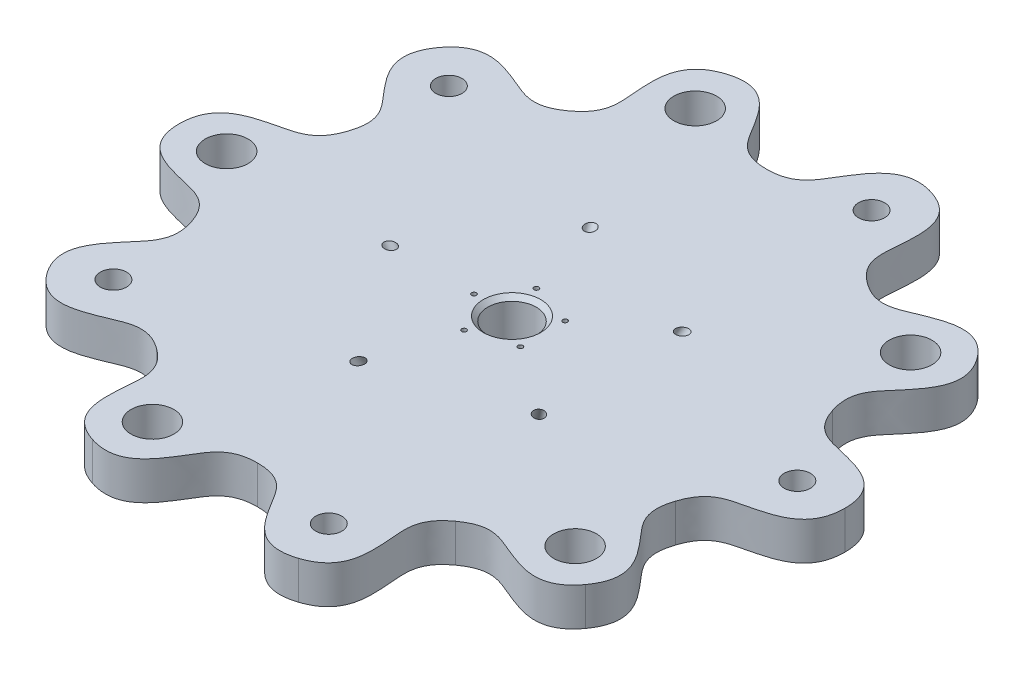
SolidWorks part; units mm, degrees
other "Markup1"
sketch "Sketch22" plane through (67.4, 16.5, 67.4) normal (0.6133, 0.6241, 0.4841) x (0.6587, -0.0661, -0.7495)
sketch "Sketch37" plane through (67.4, 28, 67.4) normal (0.6133, 0.6241, 0.4841) x (0.6587, -0.0661, -0.7495)
other "Markup2"
sketch "Sketch23" plane through (67.4, 26.5, 67.4) normal (0.1362, 0.0894, 0.9866) x (0.9893, -0.0646, -0.1307)
sketch "Sketch38" plane through (67.4, 28, 67.4) normal (0.1362, 0.0894, 0.9866) x (0.9893, -0.0646, -0.1307)
other "Markup5"
sketch "Sketch28" plane through (-67.4, 30.5, 67.4) normal (-0.0176, 0.5562, 0.8308) x (0.9998, 0.0146, 0.0115)
sketch "Sketch39" plane through (-67.4, 28, 67.4) normal (-0.0176, 0.5562, 0.8308) x (0.9998, 0.0146, 0.0115)
material "1023 Carbon Steel Sheet (SS)"
ref_plane "Front Plane" through (0, 0, 0) normal (0, 0, 1) x (1, 0, 0)
ref_plane "Top Plane" through (0, 0, 0) normal (0, 1, 0) x (1, 0, 0)
ref_plane "Right Plane" through (0, 0, 0) normal (1, 0, 0) x (0, 0, -1)
sketch "Sketch1" plane through (0, 0, 0) normal (0, 0, 1) x (1, 0, 0)
  line L5 (-47.4, 0) -> (-47.4, -8)
  line L9 (-7, -8) -> (0, -8)
  line L10 (0, -8) -> (0, 0)
  line L12 (-7, -8) -> (-17.4, -8)
  line L24 (-17.4, -8) -> (-47.4, -8)
  line L25 (-47.4, 0) -> (0, 0)
  dimension "D2" = 8
  dimension "D3" = 47.4
  dimension "D8" = 0
  dimension "D10" = 7
revolve "Revolve1" add sketch "Sketch1" angle 360 about L10
sketch "Sketch4" plane through (0, 0, 0) normal (0, 0, 1) x (1, 0, 0)
  line L0 (0, 0) -> (0, 13.3666) construction
sketch "Sketch2" plane through (0, 0, 0) normal (0, 1, 0) x (1, 0, 0)
  circle A0 centre (-8, 0) radius 0.5
  dimension "D2" = 1
  dimension "D1" = 8
extrude "Fuel holes" cut sketch "Sketch2" against normal up to next from offset 5
pattern_circular "CirPattern1" count 5 over 360 about axis through (0, 0, 0) along (0, 1, 0) of "Fuel holes" reverse direction yes
sketch "Sketch5" plane through (0, 0, 0) normal (1, 0, 0) x (0, 0, -1)
sketch "Sketch19" plane through (0, -8, 0) normal (0, -1, 0) x (1, 0, 0)
  line L0 (-47.4, 0) -> (-70, 0) construction
  line L1 (-56.6312, -41.145) -> (0, 0) construction
  line L4 (0, 0) -> (-66.574, -21.6312) construction
  line L5 (-51.8483, -13.5569) -> (-50.8815, -16.5324) construction
  line L9 (-69, 0) -> (-70, 0)
  line L11 (-53.7996, 39.0877) -> (-54.2257, 38.5013)
  circle A1 centre (0, 0) radius 47.4
  circle A2 centre (0, 0) radius 70 construction
  circle A3 centre (-60, 0) radius 4.5
  circle A4 centre (0, 0) radius 47.4 construction
  circle A5 centre (-48.541, -35.2671) radius 2.75
  circle A6 centre (0, 0) radius 53.5
  circle A8 centre (0, 0) radius 70
  spline S0 degree 3 poles (-50.8815, -16.5324) (-52.4491, -11.7078) (-59.9998, -9.5551) (-70, -7.7496) (-70, 0) knots 0 0 0 0 0.376166 1 1 1 1
  spline S1 degree 3 poles (-50.8815, -16.5324) (-49.3139, -21.357) (-54.1572, -27.5367) (-61.1863, -34.8754) (-56.6312, -41.145) knots 0 0 0 0 0.376166 1 1 1 1
  point P19 (-58.4763, -10.1374)
  point P21 (0, 0)
  point P22 (0, 0)
  circle M22 centre (0, 0) radius 47.4
  dimension "D2" = 9
  dimension "D5" = 5.5
  dimension "D7" = 107
  dimension "D3" = 60
  dimension "D4" = 36
  dimension "D6" = 60
  dimension "D8" = 18
  dimension "D1" = 22.6
extrude "Boss-Extrude2" add sketch "Sketch19" against normal blind 8 contours A6 S1 A8 S0 A3 A5 | S1 S0 A8 | A3 | A5 | A6 M22 region at (-60, -8, 0) region at (-48.541, -8, -35.2671) region at (8.1325, -8, -51.3467) region at (-61.1052, -8, -7.4539) region at (-60.0877, -8, -19.5238)
extrude "Bolt holes" cut sketch "Sketch19<3>" against normal up to surface (8 mm away) contours A3 | A5 up to face at (-1.9721, 0, -7.6085)
sketch "Sketch19<3>" plane through (0, -8, 0) normal (0, -1, 0) x (1, 0, 0) same geometry as "Sketch19"
extrude "Grooves" cut sketch "Sketch19<8>" against normal through all contours S1 S0 A8 region at (-60.0877, -8, -19.5238)
sketch "Sketch19<8>" plane through (0, -8, 0) normal (0, -1, 0) x (1, 0, 0) same geometry as "Sketch19"
sketch "Sketch21" plane through (0, 0, 0) normal (0, 0, 1) x (1, 0, 0)
  line L0 (0, 0) -> (51.8972, 0) construction
  line L1 (0, 0) -> (0, -5.4672) construction
sketch "Sketch8" plane through (-29.8564, -8, 0) normal (0, -1, 0) x (-1, 0, 0)
  line L0 (-29.8564, 0) -> (-8.8564, 0) construction
  line L1 (-8.8564, 0) -> (-8.8564, 32.0516) construction
  circle A2 centre (-8.8564, 0) radius 1.75
  dimension "D1" = 3.5
  dimension "D2" = 21
ref_plane "Plane1" through (-21, 0, 0) normal (1, 0, 0) x (0, 0, -1)
ref_plane "Plane2" through (-1.7859, 3.0933, 0) normal (0.5, -0.866, 0) x (0, 0, -1)
sketch "Sketch41" plane through (-1.7859, 3.0933, 0) normal (0.5, -0.866, 0) x (0, 0, -1)
  circle A0 centre (0, -22.1865) radius 1.15
  dimension "D1" = 2.3
extrude "Cut-Extrude7" cut sketch "Sketch41" against normal blind 10 and the other way through all
sketch "Sketch31" plane through (0, -8, 0) normal (0, -1, 0) x (1, 0, 0)
  circle A0 centre (0, 0) radius 27.4
  dimension "D1" = 54.8
sketch "Sketch32" plane through (0, 0, 0) normal (0, 1, 0) x (1, 0, 0)
  circle A0 centre (0, 0) radius 4.4
  dimension "D1" = 8.8
hole_wizard "M12 Tapped Hole1" positions "Sketch43" profile "Sketch44" tap size "M12" standard "ISO" end condition through all
sketch "Sketch43" plane through (0, 0, 0) normal (0, 1, 0) x (1, 0, 0)
  point P0 (0, 0)
sketch "Sketch44" plane through (0, 0, 0) normal (1, 0, 0) x (0, 0, 1)
  line L0 (0, 0) -> (0, 8)
  line L1 (0, 8) -> (5.1, 8)
  line L2 (5.1, 8) -> (5.1, 0.925)
  line L3 (5.1, 0.925) -> (6.025, 0)
  line L5 (6.025, 0) -> (0, 0)
  line L6 (-5.1, 0.925) -> (-6.025, 0) construction
  line L11 (0, -6.35) -> (0, 107.95) construction
  dimension "Thru Tap Drill Dia." = 10.2
  dimension "Thru Tap Drill Depth" = 8
  dimension "Near C'Sink Dia." = 12.05
  dimension "Near C'Sink Angle" = 90
cosmetic thread "Hole Thread1" parameters "D2"=12
sketch "Sketch35" plane through (0, 0, 0) normal (0, 0, 1) x (1, 0, 0)
  line L0 (0, 0) -> (0, 22.3821) construction
pattern_circular "CirPattern9" count 5 over 360 about axis through (0, 0, 0) along (0, 1, 0) of "Cut-Extrude7"
pattern_circular "CirPattern10" count 5 over 360 about axis through (0, 0, 0) along (0, 1, 0) of "Bolt holes"
pattern_circular "CirPattern11" count 10 over 360 about axis through (0, 0, 0) along (0, 1, 0) of "Grooves"
equation "\"Bolts\"= 10"
equation "\"D4@Sketch19\"=360/\"Bolts\""
equation "\"D7@Sketch19\"=102+2.5*2"
equation "\"D8@Sketch19\"=\"D4@Sketch19\"/2"
